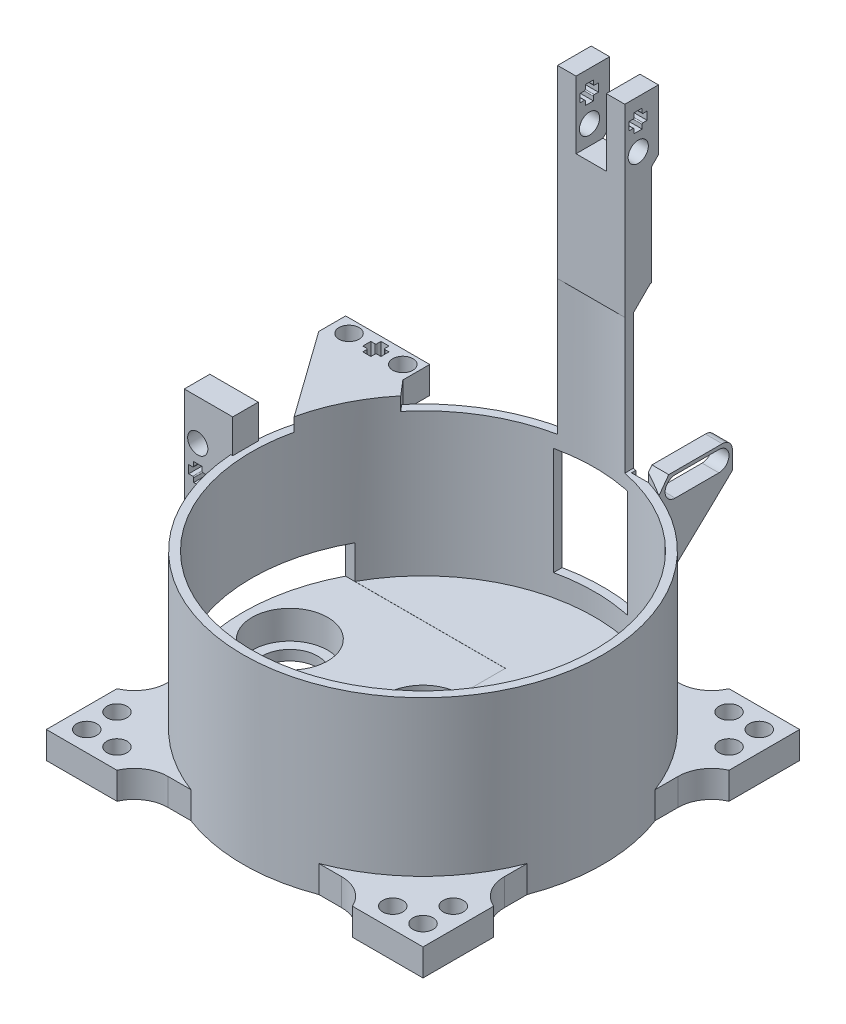
SolidWorks part; units mm, degrees
ref_plane "Front Plane" through (0, 0, 0) normal (0, 0, 1) x (1, 0, 0)
ref_plane "Top Plane" through (0, 0, 0) normal (0, 1, 0) x (1, 0, 0)
ref_plane "Right Plane" through (0, 0, 0) normal (1, 0, 0) x (0, 0, -1)
sketch "Sketch1" plane through (0, 0, 0) normal (0, 1, 0) x (1, 0, 0)
  circle A4 centre (0, 0) radius 8.25
  circle A5 centre (0, 0) radius 53.5
  circle A6 centre (-39.5911, 0) radius 8.25
extrude "Boss-Extrude1" add sketch "Sketch1" along normal blind 3
sketch "Sketch2" plane through (0, 3, 0) normal (0, 1, 0) x (1, 0, 0)
  circle A0 centre (0, 0) radius 11.25
  circle A1 centre (-39.5911, 0) radius 11.25
  circle A2 centre (0, 0) radius 53.5
extrude "Boss-Extrude2" add sketch "Sketch2" along normal blind 8.5 contours A2 | A0 | A1
sketch "Sketch3" plane through (0, 11.5, 0) normal (0, 1, 0) x (1, 0, 0)
  circle A0 centre (0, 0) radius 53.5
  circle A1 centre (0, 0) radius 51
  dimension "D1" = 2.5
extrude "Boss-Extrude3" add sketch "Sketch3" along normal blind 42.5
sketch "Sketch5" plane through (0, 11.5, 0) normal (0, 1, 0) x (1, 0, 0)
  line L0 (0, 0) -> (32.0006, 0)
sketch "Sketch6" plane through (0, 0, 0) normal (0, 0, 1) x (1, 0, 0)
  line L1 (-11, 28) -> (11, 28)
  line L2 (-11, 28) -> (-11, 50)
  line L3 (-11, 50) -> (11, 50)
  line L4 (11, 50) -> (11, 28)
  dimension "D1" = 22
extrude "Cut-Extrude1" cut sketch "Sketch6" against normal blind 85.5
sketch "Sketch7" plane through (0, 0, 0) normal (1, 0, 0) x (0, 0, -1)
  line L4 (24.5, 11.464) -> (24.5, 21.464)
  line L6 (-24.5, 11.464) -> (-24.5, 21.464)
  line L7 (-24.5, 21.464) -> (24.5, 21.464)
  line L8 (-24.5, 11.464) -> (24.5, 11.464)
extrude "Cut-Extrude2" cut sketch "Sketch7" against normal blind 120
sketch "Sketch8" plane through (0, 54, 0) normal (0, 1, 0) x (1, 0, 0)
  line L1 (-67.1822, 3.8) -> (-52.783, 3.8)
  line L2 (-67.1822, 3.8) -> (-67.1822, -3.8)
  line L3 (-67.1822, -3.8) -> (-52.783, -3.8)
  line L4 (-52.783, 3.8) -> (-52.783, -3.8)
extrude "Boss-Extrude4" add sketch "Sketch8" along normal blind 10 and the other way blind 29
sketch "Sketch9" plane through (0, 0, -3.8) normal (0, 0, -1) x (-1, 0, 0)
  line L0 (61.9718, 46.7023) -> (64.3718, 46.7023)
  line L1 (64.3718, 46.7023) -> (64.3718, 45.5023)
  line L2 (60.4718, 45.2023) -> (60.4718, 42.8023)
  line L3 (61.6718, 45.2023) -> (60.4718, 45.2023)
  line L4 (64.6718, 45.2023) -> (65.8718, 45.2023)
  line L5 (65.8718, 45.2023) -> (65.8718, 42.8023)
  line L6 (61.9718, 41.3023) -> (61.9718, 42.5023)
  line L7 (61.9718, 46.7023) -> (61.9718, 45.5023)
  line L8 (64.6718, 42.8023) -> (65.8718, 42.8023)
  line L9 (61.6718, 42.8023) -> (60.4718, 42.8023)
  line L10 (64.3718, 41.3023) -> (64.3718, 42.5023)
  line L11 (61.9718, 41.3023) -> (64.3718, 41.3023)
  line L12 (63.1822, 52) -> (63.1822, 63.9977)
  line L13 (63.1822, 52) -> (67.1822, 52)
  line L14 (67.1822, 64) -> (52.783, 64)
  line L15 (52.783, 54) -> (52.783, 64) construction
  line L16 (52.783, 64) -> (67.1822, 64) construction
  line L17 (67.1822, 25) -> (67.1822, 64) construction
  arc A0 (64.3718, 45.5023) -> (64.6718, 45.2023) centre (64.6718, 45.5023) ccw
  arc A1 (61.9718, 45.5023) -> (61.6718, 45.2023) centre (61.6718, 45.5023) cw
  arc A2 (61.9718, 42.5023) -> (61.6718, 42.8023) centre (61.6718, 42.5023) ccw
  arc A3 (64.3718, 42.5023) -> (64.6718, 42.8023) centre (64.6718, 42.5023) cw
  circle A4 centre (63.1822, 52) radius 3
  circle A5 centre (63.1822, 36) radius 3
  dimension "D1" = 4
  dimension "D2" = 12
extrude "Cut-Extrude3" cut sketch "Sketch9" against normal blind 46 contours L12 A4 L13 | L13 A4 L12 | L10 A3 L8 L5 L4 A0 L1 L0 L7 A1 L3 L2 L9 A2 L6 L11 | A5 region at (-63.1718, 44.0023, -3.8) region at (-62.7577, 51.5756, -3.8) region at (-64.4554, 53.2732, -3.8) region at (-63.1822, 36, -3.8)
sketch "Sketch12" plane through (0, 54, 0) normal (0, 1, 0) x (1, 0, 0)
  line L4 (-43, 45) -> (-47, 45)
  line L8 (-43, 41) -> (-43, 45)
  line L9 (-57.6977, 39.7897) -> (-57.6977, 42.1897)
  line L10 (-57.6977, 42.1897) -> (-56.4977, 42.1897)
  line L11 (-56.1977, 39.4897) -> (-56.1977, 38.2897)
  line L28 (-56.1977, 42.4897) -> (-56.1977, 43.6897)
  line L29 (-52.2977, 39.7897) -> (-53.4977, 39.7897)
  line L30 (-57.6977, 39.7897) -> (-56.4977, 39.7897)
  line L31 (-53.7977, 43.6897) -> (-56.1977, 43.6897)
  line L32 (-53.7977, 42.4897) -> (-53.7977, 43.6897)
  line L33 (-53.7977, 39.4897) -> (-53.7977, 38.2897)
  line L34 (-53.7977, 38.2897) -> (-56.1977, 38.2897)
  line L35 (-52.2977, 42.1897) -> (-53.4977, 42.1897)
  line L36 (-52.2977, 39.7897) -> (-52.2977, 42.1897)
  line L37 (-68, 37) -> (-68, 45)
  line L38 (-43, 45) -> (-43, 37)
  line L39 (-68, 45) -> (-43, 45)
  line L40 (-39.221, 32.5993) -> (-43, 37)
  line L41 (-68, 37) -> (-49.7075, 11.4091)
  circle A7 centre (-63, 41) radius 3
  circle A8 centre (-47, 41) radius 3
  arc A9 (-56.4977, 42.1897) -> (-56.1977, 42.4897) centre (-56.4977, 42.4897) ccw
  arc A10 (-56.4977, 39.7897) -> (-56.1977, 39.4897) centre (-56.4977, 39.4897) cw
  arc A11 (-53.4977, 39.7897) -> (-53.7977, 39.4897) centre (-53.4977, 39.4897) ccw
  arc A12 (-53.4977, 42.1897) -> (-53.7977, 42.4897) centre (-53.4977, 42.4897) cw
  arc A13 (-49.7075, 11.4091) -> (-39.221, 32.5993) centre (0, 0) cw
  arc M10 (-53.3649, -3.8) -> (-53.3649, 3.8) centre (0, 0) ccw
  circle M11 centre (0, 0) radius 51
extrude "Boss-Extrude6" add sketch "Sketch12" along normal blind 4 and the other way blind 4 contours L37 L41 L40 L38 L8 L4 L39 A12 L35 L36 L29 A11 L33 L34 L11 A10 L30 L9 L10 A9 L28 L31 L32 A7 A8 M10 | L41 L40 M10 M11 region at (-54.2688, 54, -32.8843) region at (-46.1382, 54, -23.5517)
sketch "Sketch14" plane through (0, 50, 0) normal (0, -1, 0) x (1, 0, 0)
  line L0 (-68, -37) -> (-43, -37)
  line L1 (-43, -37) -> (-40.8718, -34.5217)
  line L2 (-68, -37) -> (-51.6147, -14.0773)
  circle A0 centre (0, 0) radius 53.5 construction
  arc A1 (-51.6147, -14.0773) -> (-40.8718, -34.5217) centre (0, 0) ccw construction
  arc A2 (-51.6147, -14.0773) -> (-40.8718, -34.5217) centre (0, 0) ccw
extrude "Boss-Extrude7" add sketch "Sketch14" along normal blind 0.1
chamfer "Chamfer1" distance 24 angle 45 1 edges at (-47.3596, 49.9, -24.8861)
sketch "Sketch15" plane through (0, 0, 0) normal (0, -1, 0) x (1, 0, 0)
  line L0 (50, -43.9917) -> (50, -44)
  line L12 (50, -19.0329) -> (50, -35)
  line L13 (50, -44) -> (50, -43.9917)
  line L14 (35, 50) -> (19.0329, 50)
  line L17 (56, -35) -> (50, -35)
  line L18 (35, 50) -> (35, 56)
  line L23 (56, 56) -> (35, 56)
  line L24 (56, -35) -> (56, -56)
  line L25 (56, -56) -> (35, -56)
  line L27 (35, -50) -> (35, -56)
  line L28 (35, -50) -> (19.0329, -50)
  line L32 (56, 35) -> (56, 56)
  line L33 (56, 35) -> (50, 35)
  line L34 (50, 44) -> (50, 43.9917)
  line L35 (50, 19.0329) -> (50, 35)
  line L36 (50, 43.9917) -> (50, 44)
  line L37 (-56, 56) -> (-35, 56)
  line L38 (-50, 19.0329) -> (-50, 35)
  line L39 (-50, 44) -> (-50, 43.9917)
  line L40 (-56, 35) -> (-50, 35)
  line L41 (-56, 35) -> (-56, 56)
  line L42 (-35, 50) -> (-35, 56)
  line L43 (-35, 50) -> (-19.0329, 50)
  line L44 (-35, -50) -> (-19.0329, -50)
  line L45 (-35, -50) -> (-35, -56)
  line L46 (-56, -56) -> (-35, -56)
  line L47 (-56, -35) -> (-56, -56)
  line L48 (-56, -35) -> (-50, -35)
  line L49 (-50, -44) -> (-50, -43.9917)
  line L50 (-50, -19.0329) -> (-50, -35)
  line L51 (-50, -43.9917) -> (-50, -44)
  arc A2 (19.0329, -50) -> (50, -19.0329) centre (0, 0) ccw
  circle A7 centre (50, -50) radius 3
  circle A8 centre (50, -41) radius 3
  circle A9 centre (41, -50) radius 3
  circle A22 centre (41, 50) radius 3
  circle A23 centre (50, 41) radius 3
  circle A24 centre (50, 50) radius 3
  arc A25 (19.0329, 50) -> (50, 19.0329) centre (0, 0) cw
  arc A26 (-19.0329, 50) -> (-50, 19.0329) centre (0, 0) ccw
  circle A27 centre (-50, 50) radius 3
  circle A28 centre (-50, 41) radius 3
  circle A29 centre (-41, 50) radius 3
  circle A30 centre (-41, -50) radius 3
  circle A31 centre (-50, -41) radius 3
  circle A32 centre (-50, -50) radius 3
  arc A33 (-19.0329, -50) -> (-50, -19.0329) centre (0, 0) cw
  circle M22 centre (0, 0) radius 53.5
  dimension "D1" = 9
  dimension "D2" = 9
  dimension "D4" = 6
  dimension "D6" = 6
extrude "Boss-Extrude9" add sketch "Sketch15" against normal blind 8 contours L50 L48 L47 L46 L45 L44 A31 A30 A32 M22 | L43 L42 L37 L41 L40 L38 A29 A28 A27 M22 | L35 L33 L32 L23 L18 L14 A23 A22 A24 M22 | L28 L27 L25 L24 L17 L12 A9 A8 A7 M22 region at (43.5719, 0, -43.5719) region at (-43.5719, 0, -43.5719) region at (43.5719, 0, 43.5719) region at (-43.5719, 0, 43.5719)
fillet "Fillet2" radius 10 8 edges at (-35, 4, -50) (-50, 4, -35) (-35, 4, 50) (-50, 4, 35) (50, 4, 35) (35, 4, 50) (50, 4, -35) (35, 4, -50)
sketch "Sketch17" plane through (0, 54, 0) normal (0, 1, 0) x (1, 0, 0)
  line L0 (10, 52.5571) -> (10, 50.01)
  line L1 (-10, 52.5571) -> (-10, 50.01)
  arc A0 (10, 50.01) -> (-10, 50.01) centre (0, 0) ccw
  arc A1 (10, 52.5571) -> (-10, 52.5571) centre (0, 0) ccw
extrude "Boss-Extrude10" add sketch "Sketch17" along normal blind 95
sketch "Sketch18" plane through (0, 0, 0) normal (1, 0, 0) x (0, 0, -1)
  line L52 (50.01, 149) -> (50.01, 94.1062)
  line L60 (50.01, 149) -> (60.01, 149)
  line L69 (50.01, 149) -> (50.01, 94.1062)
  line L85 (58.01, 99) -> (57.5571, 99)
  line L86 (60.01, 131) -> (60.01, 149)
  line L87 (58.01, 129) -> (60.01, 131)
  line L88 (58.01, 99) -> (58.01, 129)
  line L89 (52.5571, 94) -> (57.5571, 99)
  line L90 (52.5571, 94) -> (50.01, 94.1062)
extrude "Boss-Extrude13" add sketch "Sketch18" along normal blind 10 and the other way blind 10 contours L90 L89 L85 L88 L87 L86 L60 L52 region at (0, 123.8038, -54.3505)
sketch "Sketch19" plane through (10, 0, 0) normal (1, 0, 0) x (0, 0, -1)
  line L1 (51.2555, 143.9379) -> (51.2555, 141.5379)
  line L2 (51.2555, 143.9379) -> (52.4555, 143.9379)
  line L3 (52.7555, 144.2379) -> (52.7555, 145.4379)
  line L4 (51.2555, 141.5379) -> (52.4555, 141.5379)
  line L5 (52.7555, 141.2379) -> (52.7555, 140.0379)
  line L6 (55.1555, 145.4379) -> (52.7555, 145.4379)
  line L7 (55.1555, 144.2379) -> (55.1555, 145.4379)
  line L8 (56.6555, 143.9379) -> (55.4555, 143.9379)
  line L12 (55.1555, 140.0379) -> (52.7555, 140.0379)
  line L13 (55.1555, 141.2379) -> (55.1555, 140.0379)
  line L14 (56.6555, 141.5379) -> (55.4555, 141.5379)
  line L15 (56.6555, 143.9379) -> (56.6555, 141.5379)
  arc A0 (52.7555, 144.2379) -> (52.4555, 143.9379) centre (52.4555, 144.2379) cw
  arc A1 (52.7555, 141.2379) -> (52.4555, 141.5379) centre (52.4555, 141.2379) ccw
  arc A2 (55.1555, 144.2379) -> (55.4555, 143.9379) centre (55.4555, 144.2379) ccw
  arc A3 (55.1555, 141.2379) -> (55.4555, 141.5379) centre (55.4555, 141.2379) cw
  circle A4 centre (54.01, 134.776) radius 3
  point P26 (53.9555, 145.4379)
  point P27 (53.9555, 140.0379)
  point P28 (56.6555, 142.7379)
extrude "Cut-Extrude4" cut sketch "Sketch19" against normal blind 20 contours L1 L4 A1 L5 L12 L13 A3 L14 L15 L8 A2 L7 L6 L3 A0 L2 | A4
sketch "Sketch20" plane through (0, 149, 0) normal (0, 1, 0) x (1, 0, 0)
  line L3 (-4.5, 60.01) -> (-4.5, 50.01)
  line L4 (4.5, 60.01) -> (4.5, 50.01)
  line L5 (-4.5, 60.01) -> (4.5, 60.01)
  line L6 (4.5, 50.01) -> (-4.5, 50.01)
extrude "Cut-Extrude5" cut sketch "Sketch20" against normal blind 20
sketch "Sketch23" plane through (0, 58, 0) normal (0, 1, 0) x (1, 0, 0)
  line L1 (15.9035, 51.0816) -> (15.9035, 71.0816)
  line L2 (15.9035, 71.0816) -> (20.9035, 71.0816)
  line L3 (20.9035, 71.0816) -> (20.9035, 49.2473)
  arc A1 (20.9035, 49.2473) -> (15.9035, 51.0816) centre (0, 0) ccw
  dimension "D1" = 20
extrude "Boss-Extrude14" add sketch "Sketch23" against normal blind 8
sketch "Sketch25" plane through (20.9035, 0, 0) normal (1, 0, 0) x (0, 0, -1)
  line L0 (54.0816, 54) -> (67.0816, 54) construction
  line L1 (54.0816, 57) -> (67.0816, 57)
  line L2 (54.0816, 51) -> (67.0816, 51)
  line L3 (71.0816, 50) -> (71.0816, 58) construction
  line L4 (49.2473, 58) -> (71.0816, 58) construction
  line L7 (49.2473, 58) -> (49.2473, 54)
  line L8 (49.2473, 58) -> (52.1662, 58)
  line L9 (49.2473, 54) -> (52.1662, 58)
  arc A0 (54.0816, 57) -> (54.0816, 51) centre (54.0816, 54) ccw
  arc A1 (67.0816, 51) -> (67.0816, 57) centre (67.0816, 54) ccw
  point P2 (60.5816, 54)
  dimension "D1" = 4
  dimension "D2" = 3
  dimension "D3" = 1
  dimension "D4" = 13
extrude "Cut-Extrude6" cut sketch "Sketch25" against normal blind 10
chamfer "Chamfer2" distance 21 angle 45 1 edges at (18.4264, 50, -50.2267)
fillet "Fillet3" radius 3 1 edges at (18.4035, 58, -71.0816)
sketch "Sketch26" plane through (0, 11.5, 0) normal (0, 1, 0) x (1, 0, 0)
  line L0 (56, 56) -> (56, -56)
  line L1 (56, 0) -> (-67.1822, 0)
  line L2 (-67.1822, 3.8) -> (-67.1822, -3.8) construction
  line L3 (-67.1822, 0) -> (-100.1822, 0)
  line L4 (-66, 41) -> (-111, 41)
  line L5 (-66, 41) -> (56, 41)
  line L6 (15.9035, 71.0816) -> (15.9035, -56)
  circle A0 centre (-63, 41) radius 3 construction
sketch "Sketch27" plane through (0, 0, 0) normal (0, 0, 1) x (1, 0, 0)
  line L0 (11, 28) -> (11, 50) construction
  line L1 (-11, 28) -> (11, 28)
  line L2 (-11, 28) -> (-11, 18)
  line L3 (-11, 18) -> (11, 18)
  line L4 (11, 28) -> (11, 18)
  line L5 (-11, 50) -> (11, 50) construction
  dimension "D1" = 32
extrude "Cut-Extrude7" cut sketch "Sketch27" against normal up to next
